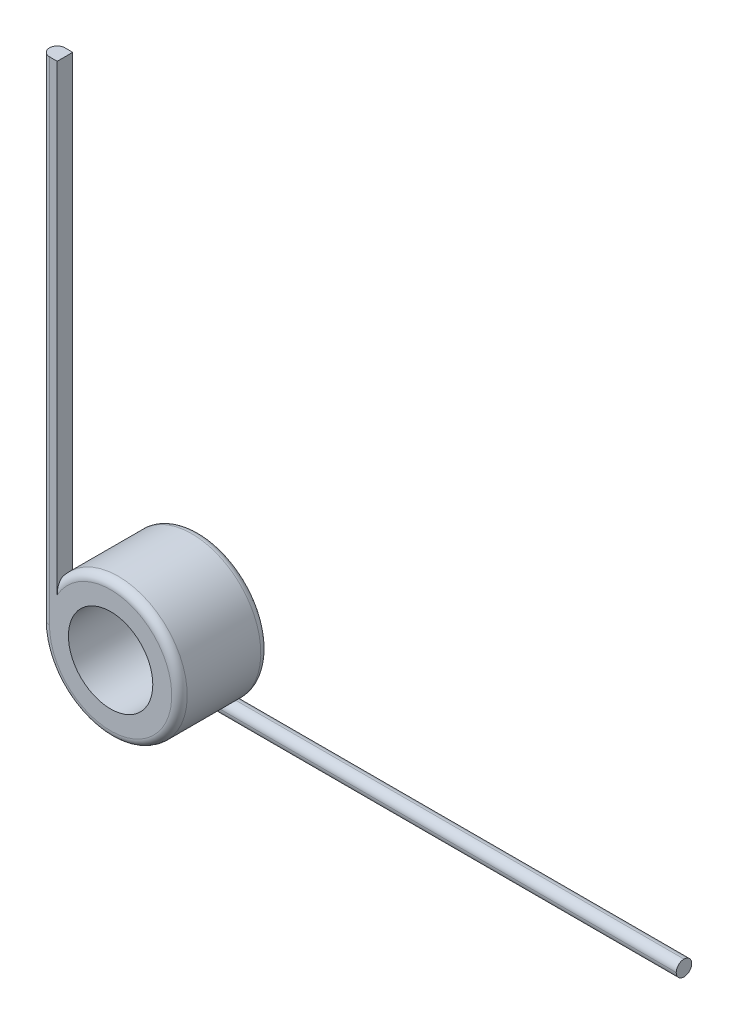
SolidWorks part; units mm, degrees
ref_plane "Front Plane" through (0, 0, 0) normal (0, 0, 1) x (1, 0, 0)
ref_plane "Top Plane" through (0, 0, 0) normal (0, 1, 0) x (1, 0, 0)
ref_plane "Right Plane" through (0, 0, 0) normal (1, 0, 0) x (0, 0, -1)
sketch "Sketch1" plane through (0, 0, 0) normal (0, 0, 1) x (1, 0, 0)
  circle A0 centre (0, 0) radius 7.112
  circle A1 centre (0, 0) radius 4.3561
  dimension "D1" = 14.224
  dimension "D2" = 8.7122
extrude "Boss-Extrude1" add sketch "Sketch1" along normal blind 9.1948
sketch "Sketch2" plane through (0, 0, 9.1948) normal (0, 0, 1) x (1, 0, 0)
  line L0 (-7.112, 0) -> (-7.112, 50.8)
  line L1 (-7.112, 50.8) -> (-5.5118, 50.8)
  line L2 (-5.5118, 50.8) -> (-5.5118, 4.4945)
  line L3 (0, 0) -> (0, -14.6657) construction
  circle A0 centre (0, 0) radius 7.112 construction
  arc A1 (-5.5118, 4.4945) -> (-7.112, 0) centre (0, 0) ccw
  dimension "D1" = 50.8
  dimension "D2" = 1.6002
  dimension "D3" = 180
extrude "Boss-Extrude2" add sketch "Sketch2" against normal blind 1.6002
fillet "Fillet1" radius 0.8001 3 edges at (6.7, -2.3854, 9.1948) (-7.112, 25.4, 7.5946) (-7.112, 25.4, 9.1948)
sketch "Sketch4" plane through (0, 0, 0) normal (0, 0, -1) x (-1, 0, 0)
  line L0 (0, -7.112) -> (-50.8, -7.112)
  line L1 (-50.8, -7.112) -> (-50.8, -5.5118)
  line L2 (-50.8, -5.5118) -> (-4.4945, -5.5118)
  circle A0 centre (0, 0) radius 7.112 construction
  arc A1 (-4.4945, -5.5118) -> (0, -7.112) centre (0, 0) ccw
  dimension "D1" = 1.6002
  dimension "D2" = 50.8
extrude "Boss-Extrude4" add sketch "Sketch4" against normal blind 1.6002
fillet "Fillet2" radius 0.8001 5 edges at (-2.3854, 6.7, 0) (25.4, -7.112, 1.6002) (27.6473, -5.5118, 1.6002) (25.4, -7.112, 0) (27.6473, -5.5118, 0)
equation "\"diam\"= .063"
equation "\"shaft\"= .343"
equation "\"od\"= .56"
equation "\"length\"= .362"
equation "\"D1@Sketch1\"=\"od\""
equation "\"D2@Sketch1\"=\"shaft\""
equation "\"coils\"= 8"
equation "\"D1@Boss-Extrude1\"=\"length\""
equation "\"D1@Boss-Extrude2\"=\"diam\""
equation "\"D2@Sketch2\"=\"diam\""
equation "\"arm\"= 2"
equation "\"D1@Sketch2\"=\"arm\""
equation "\"D2@Sketch4\"=\"arm\""
equation "\"D1@Sketch4\"=\"diam\""
equation "\"D1@Boss-Extrude4\"=\"diam\""
equation "\"D1@Fillet2\"=\"diam\"/2"
equation "\"D1@Fillet1\"=\"diam\"/2"
